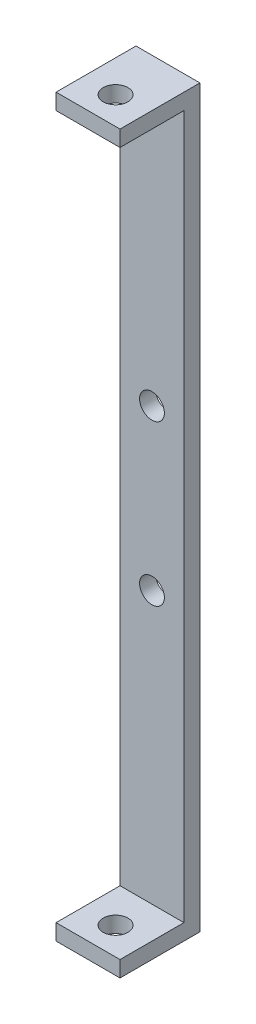
SolidWorks part; units mm, degrees
ref_plane "前视基准面" through (0, 0, 0) normal (0, 0, 1) x (1, 0, 0)
ref_plane "上视基准面" through (0, 0, 0) normal (0, 1, 0) x (1, 0, 0)
ref_plane "右视基准面" through (0, 0, 0) normal (1, 0, 0) x (0, 0, -1)
other "Configuration Table"
sketch "草图1" plane through (0, 0, 0) normal (1, 0, 0) x (0, 0, -1)
  line L0 (0, 0) -> (10, 0)
  line L1 (10, 0) -> (10, 92)
  line L2 (10, 92) -> (0, 92)
  line L3 (0, 92) -> (0, 90)
  line L4 (0, 90) -> (8, 90)
  line L5 (8, 90) -> (8, 2)
  line L6 (8, 2) -> (0, 2)
  line L7 (0, 2) -> (0, 0)
  dimension "D1" = 10
  dimension "D2" = 92
  dimension "D3" = 2
  dimension "D4" = 8
  dimension "D5" = 88
extrude "凸台-拉伸2" add sketch "草图1" along normal blind 8
sketch3d "3D草图1"
  line L0 (4, 0, 0) -> (4, 0, -10) construction
  line L1 (8, 0, 0) -> (0, 0, 0) construction
  line L2 (8, 0, -10) -> (0, 0, -10) construction
  line L3 (8, 0, -5) -> (0, 0, -5) construction
  line L4 (8, 0, 0) -> (8, 0, -10) construction
  line L5 (0, 0, 0) -> (0, 0, -10) construction
  circle A0 centre (4, 0, -3.4429) radius 1.55
  point P2 (4, 1.55, -3.4429)
extrude "切除-拉伸1" cut sketch "3D草图1" along direction (0, -1, 0) on the side against the normal through all
sketch3d "3D草图2"
  line L0 (8, 46, -10) -> (0, 46, -10) construction
  line L1 (8, 0, -10) -> (8, 92, -10) construction
  line L2 (0, 0, -10) -> (0, 92, -10) construction
  line L3 (4, 46, -10) -> (4, 92, -10) construction
  line L4 (8, 92, -10) -> (0, 92, -10) construction
  line L5 (4, 46, -10) -> (4, 0, -10) construction
  line L6 (8, 0, -10) -> (0, 0, -10) construction
  circle A0 centre (4, 36, -10) radius 1.55
  circle A1 centre (4, 56, -10) radius 1.55
  point P15 (4, 36, -8.45)
  point P19 (4, 56, -8.45)
  dimension "D1" = 20
extrude "切除-拉伸2" cut sketch "3D草图2" along direction (0, 0, -1) on the side against the normal through all
